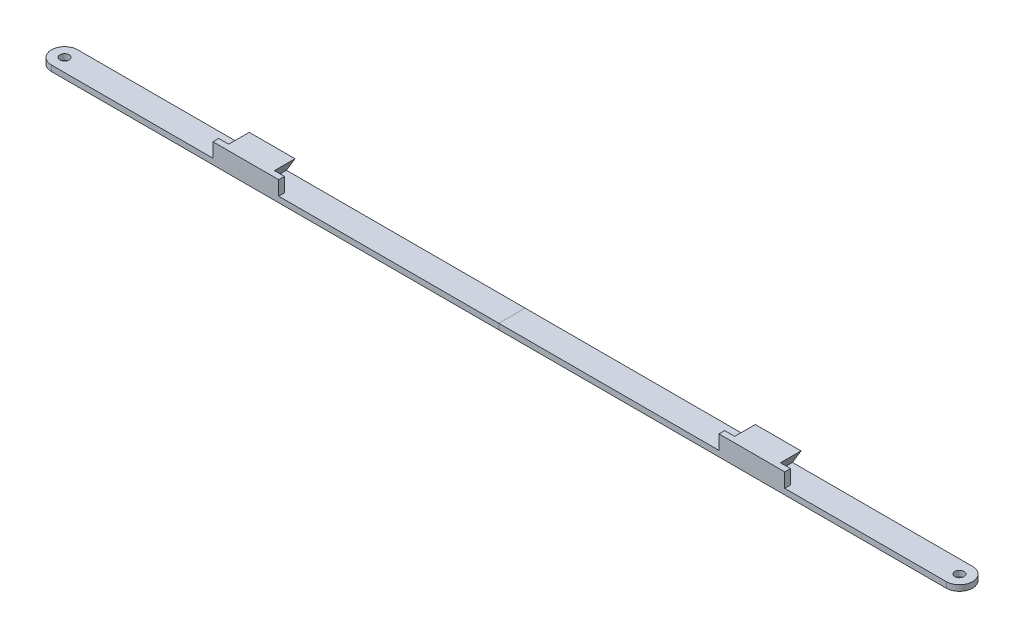
SolidWorks part; units mm, degrees
material "PLA"
ref_plane "Спереди" through (0, 0, 0) normal (0, 0, 1) x (1, 0, 0)
ref_plane "Сверху" through (0, 0, 0) normal (0, 1, 0) x (1, 0, 0)
ref_plane "Справа" through (0, 0, 0) normal (1, 0, 0) x (0, 0, -1)
sketch "Эскиз1" plane through (0, 0, 0) normal (0, 1, 0) x (1, 0, 0)
  line L0 (0, 0) -> (0, 44955.4742) construction
  line L1 (0, 0) -> (-44955.4742, 0) construction
  line L2 (-156.5, 4.6) -> (156.5, 4.6)
  line L3 (156.5, -4.6) -> (-156.5, -4.6)
  circle A0 centre (-156.5, 0) radius 1.6
  circle A1 centre (156.5, 0) radius 1.6
  arc A2 (-156.5, 4.6) -> (-156.5, -4.6) centre (-156.5, 0) ccw
  arc A3 (156.5, 4.6) -> (156.5, -4.6) centre (156.5, 0) cw
  circle A5 centre (-156.5, 0) radius 4.6 construction
  point P17 (-152.1966, 1.3157)
  dimension "D2" = 3.2
  dimension "D1" = 313
  dimension "D3" = 3
extrude "Бобышка-Вытянуть1" add sketch "Эскиз1" along normal blind 2
sketch "Эскиз2" plane through (0, 0, 4.6) normal (0, 0, 1) x (1, 0, 0)
  line L0 (0, 0) -> (0, 50000) construction
  line L1 (-156.5, 0) -> (156.5, 0) construction
  line L3 (-156.5, 2) -> (156.5, 2) construction
  line L7 (-93.5, 2) -> (-96.5, 7)
  line L8 (-96.5, 7) -> (-80.5, 7)
  line L9 (-80.5, 7) -> (-83.5, 2)
  line L10 (-83.5, 2) -> (-93.5, 2)
  line L11 (80.5, 7) -> (83.5, 2)
  line L12 (96.5, 7) -> (80.5, 7)
  line L13 (93.5, 2) -> (96.5, 7)
  line L14 (83.5, 2) -> (93.5, 2)
  point P4 (0, 0)
  point P12 (0, 2)
  dimension "D1" = 16
  dimension "D2" = 5
  dimension "D3" = 10
  dimension "D4" = 83.5
extrude "Бобышка-Вытянуть3" add sketch "Эскиз2" against normal up to surface (9.2 mm away) up to face at (0, 1, -4.6)
sketch "Эскиз3" plane through (0, 0, 4.6) normal (0, 0, 1) x (1, 0, 0)
  line L0 (-156.5, 0) -> (156.5, 0) construction
  line L1 (-100, 0) -> (-77, 0)
  line L2 (-100, 0) -> (-100, 7)
  line L3 (-100, 7) -> (-77, 7)
  line L4 (-77, 0) -> (-77, 7)
  line L6 (0, 0) -> (0, 50000) construction
  line L7 (100, 7) -> (77, 7)
  line L8 (77, 0) -> (77, 7)
  line L9 (100, 0) -> (77, 0)
  line L10 (100, 0) -> (100, 7)
  point P12 (0, 0)
  dimension "D1" = 77
  dimension "D2" = 23
extrude "Бобышка-Вытянуть4" add sketch "Эскиз3" against normal blind 2
split "Разделить1" trim tools "Справа" bodies to split 106 resulting bodies 107 108
